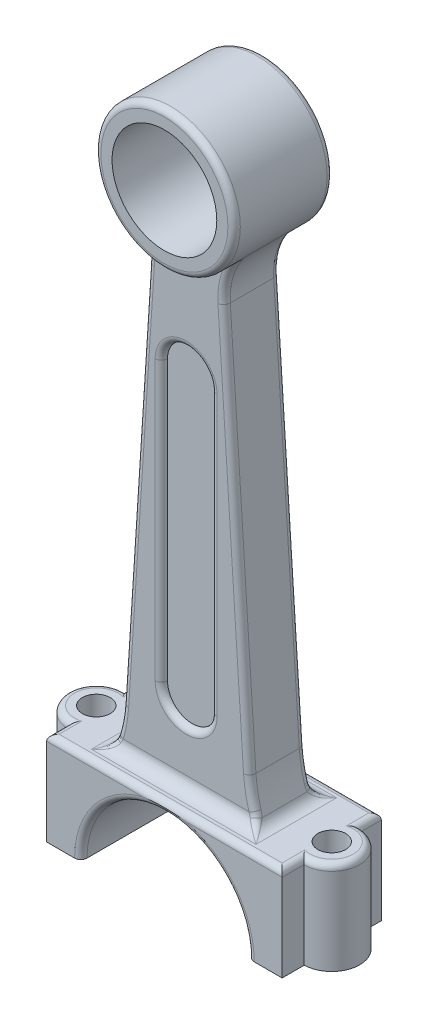
SolidWorks part; units mm, degrees
material "AISI 304"
ref_plane "Plano frontal" through (0, 0, 0) normal (0, 0, 1) x (1, 0, 0)
ref_plane "Plano superior" through (0, 0, 0) normal (0, 1, 0) x (1, 0, 0)
ref_plane "Plano direito" through (0, 0, 0) normal (1, 0, 0) x (0, 0, -1)
sketch "Esboço2" plane through (0, 0, 0) normal (0, 0, 1) x (1, 0, 0)
  line L0 (0, 100.6) -> (0, -100.6) construction
  line L3 (-140.7844, -100.4455) -> (140.7844, -100.4455) construction
  line L4 (0, 45) -> (0, -45) construction
  line L5 (8, 45) -> (8, -45)
  line L6 (-8, 45) -> (-8, -45)
  line L7 (0, 331.1946) -> (0, -386.5765) construction
  line L8 (20.538, -56.6259) -> (12.2697, 70.7318)
  line L9 (-20.538, -56.6259) -> (-12.2697, 70.7318)
  line L15 (-37.9959, -100.4455) -> (-37.9959, -70.4455)
  line L16 (-37.9959, -70.4455) -> (38.0041, -70.4455)
  line L21 (38.0041, -100.4455) -> (38.0041, -70.4455)
  line L22 (0, -100.6) -> (31.9115, -83.937) construction
  line L23 (-31.9115, -83.937) -> (0, -100.6) construction
  line L24 (-37.9959, -100.4455) -> (-37.9959, -100.6)
  line L25 (-37.9959, -100.6) -> (-27, -100.6)
  line L26 (27, -100.6) -> (38.0041, -100.6)
  line L27 (38.0041, -100.6) -> (38.0041, -100.4455)
  circle A2 centre (0, 100.6) radius 16.9
  arc A3 (27, -100.6) -> (-27, -100.6) centre (0, -100.6) ccw
  circle A4 centre (0, 100.6) radius 22.5
  arc A5 (35.9997, -100.4455) -> (-36, -100.6) centre (0, -100.6) ccw
  arc A6 (8, 45) -> (-8, 45) centre (0, 45) ccw
  arc A7 (-8, -45) -> (8, -45) centre (0, -45) ccw
  arc A8 (-17.304, 86.2187) -> (-12.2697, 70.7318) centre (-34.2235, 72.1571) cw
  arc A9 (17.304, 86.2187) -> (12.2697, 70.7318) centre (34.2235, 72.1571) ccw
  arc A10 (-23.8529, -70.4455) -> (-20.538, -56.6259) centre (-62.3083, -53.9141) ccw
  arc A11 (23.8529, -70.4455) -> (20.538, -56.6259) centre (62.3083, -53.9141) cw
  point P2 (0, 0)
  point P20 (0, 0)
  point P40 (0, -100.4455)
  dimension "D1" = 201.2
  dimension "D2" = 33.8
  dimension "D3" = 45
  dimension "D4" = 72
  dimension "D5" = 54
  dimension "D6" = 55.6
  dimension "D7" = 16
  dimension "D9" = 22
  dimension "D8" = 30
  dimension "D10" = 3.715
  dimension "D11" = 76
  dimension "D12" = 1.9959
  dimension "D13" = 2.0044
extrude "Ressalto-extrusão1" add sketch "Esboço2" along normal mid plane 32 contours A5 L16 L15 L24 L25 | L16 A5 L25 A3 L26 L27 L21 | A4 A2 region at (30.9285, -71.2446, 0) region at (0, 78.7364, 0) region at (-33.0185, -79.9165, 0)
extrude "Ressalto-extrusão2" add sketch "Esboço2<5>" along normal mid plane 18 contours L16 A11 L8 A9 A4 A8 L9 A10 A5 A7 L6 A6 L5 region at (20.0122, -64.0594, 0)
sketch "Esboço2<5>" plane through (0, 0, 0) normal (0, 0, 1) x (1, 0, 0) same geometry as "Esboço2"
extrude "Ressalto-extrusão3" add sketch "Esboço2<6>" along normal mid plane 14 contours L6 A7 L5 A6 region at (0, 0, 0)
sketch "Esboço2<6>" plane through (0, 0, 0) normal (0, 0, 1) x (1, 0, 0) same geometry as "Esboço2"
extrude "Ressalto-extrusão4" add sketch "Esboço2<7>" along normal mid plane 18 contours L16 A5 region at (0, -68.0902, 0)
sketch "Esboço2<7>" plane through (0, 0, 0) normal (0, 0, 1) x (1, 0, 0) same geometry as "Esboço2"
sketch "Esboço3" plane through (0, -70.4455, 0) normal (0, 1, 0) x (1, 0, 0)
  line L0 (-78.7254, 0) -> (88.085, 0) construction
  line L1 (0, 52.8233) -> (0, -63.4385) construction
  line L3 (-37.9959, -16) -> (-37.9959, 16) construction
  line L4 (38.0041, -16) -> (38.0041, 16) construction
  circle A0 centre (-37.9959, 0) radius 4.5
  circle A1 centre (38.0041, 0) radius 4.5
  circle A2 centre (-37.9959, 0) radius 9
  circle A3 centre (38.0041, 0) radius 9
  arc A4 (-41.7958, 8.1585) -> (-37.9959, 14.1201) centre (-44.5724, 14.1201) ccw
  arc A5 (-37.9959, -15.0649) -> (-42.2614, -7.925) centre (-46.1043, -15.0649) ccw
  arc A6 (37.9959, -15.0649) -> (42.2614, -7.925) centre (46.1043, -15.0649) cw
  arc A7 (41.7958, 8.1585) -> (37.9959, 14.1201) centre (44.5724, 14.1201) cw
  line M7 (-37.9959, 16) -> (-37.9959, -16)
  line M9 (38.0041, -16) -> (38.0041, 16)
  dimension "D1" = 18
  dimension "D2" = 9
extrude "Ressalto-extrusão5" add sketch "Esboço3" against normal blind 30 contours A2 A0 M7 | A3 A1 region at (-42.6972, -70.4455, 0) region at (41.3284, -70.4455, -3.3243)
extrude "Corte-extrusão1" cut sketch "Esboço3<5>" against normal through all contours A0 M7 | A1 M9 region at (-36.0861, -70.4455, 0) region at (36.0942, -70.4455, 0)
sketch "Esboço3<5>" plane through (0, -70.4455, 0) normal (0, 1, 0) x (1, 0, 0) same geometry as "Esboço3"
fillet "Filete1" radius 4 4 edges at (0, -70.4455, -9) (23.8529, -70.4455, 0) (0, -70.4455, 9) (-23.8529, -70.4455, 0)
fillet "Filete2" radius 2 20 edges at (-24.2708, -69.7087, -10.6866) (-21.16, -61.5905, -9) (-13.3012, 78.9582, -9) (-24.2708, -69.7087, 10.6866) (-21.16, -61.5905, 9) (-13.3012, 78.9582, 9) (24.2708, -69.7087, 10.6866) (21.16, -61.5905, 9) (13.3012, 78.9582, 9) (24.2708, -69.7087, -10.6866) (21.16, -61.5905, -9) (13.3012, 78.9582, -9) (-16.4039, 7.053, -9) (-16.4039, 7.053, 9) (16.4039, 7.053, 9) (16.4039, 7.053, -9)
fillet "Filete3" radius 2 2 edges at (22.5, 100.6, -16) (22.5, 100.6, 16)
fillet "Filete4" radius 2 10 edges at (-37.9959, -70.4455, -12.5) (-37.9959, -70.4455, 12.5) (-46.9959, -70.4455, 0) (0.0041, -70.4455, 16) (0.0041, -70.4455, -16) (38.0041, -70.4455, -12.5) (38.0041, -70.4455, 12.5) (47.0041, -70.4455, 0) (0, -73.6, -16) (0, -73.6, 16)
fillet "Filete5" radius 2 8 edges at (0, 53, -9) (8, 0, -9) (0, -53, -9) (8, 0, 9) (0, -53, 9) (-8, 0, 9) (-8, 0, -9) (0, 53, 9)
fillet "Filete6" radius 1 4 edges at (38.0041, -100.4455, 6.75) (-37.9959, -100.4455, 6.75) (-37.9959, -100.4455, -6.75) (38.0041, -100.4455, -6.75)
